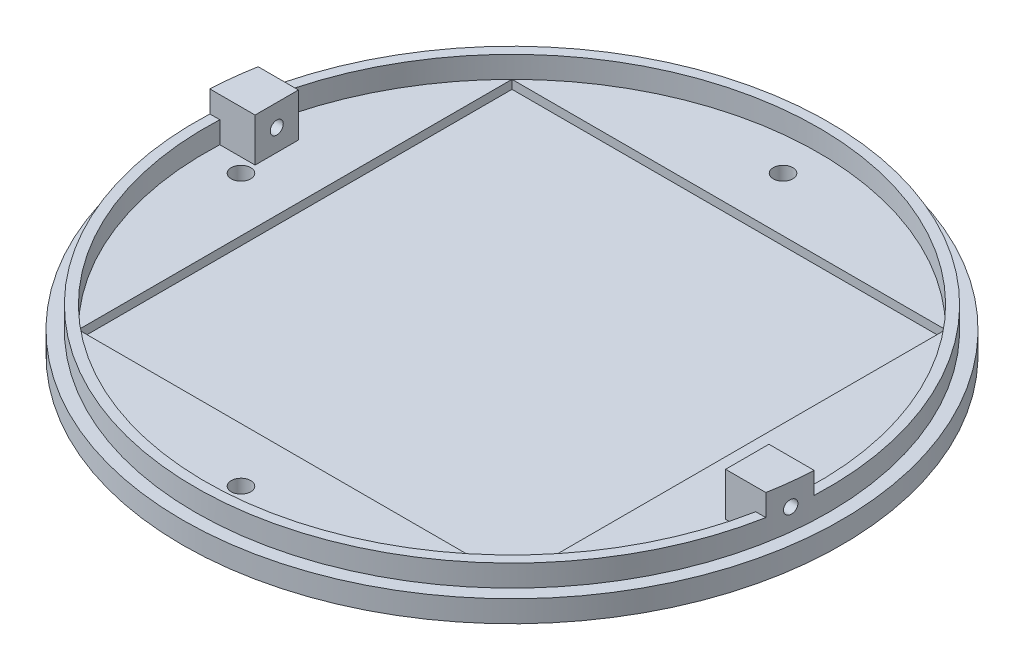
SolidWorks part; units mm, degrees
material "Custom Plastic"
ref_plane "Front Plane" through (0, 0, 0) normal (0, 0, 1) x (1, 0, 0)
ref_plane "Top Plane" through (0, 0, 0) normal (0, 1, 0) x (1, 0, 0)
ref_plane "Right Plane" through (0, 0, 0) normal (1, 0, 0) x (0, 0, -1)
sketch "Sketch1" plane through (0, 0, 0) normal (0, 1, 0) x (1, 0, 0)
  line L0 (0, 0) -> (0, -17.9724) construction
  line L1 (-50, -50) -> (50, -50)
  line L2 (-50, -50) -> (-50, 50)
  line L3 (-50, 50) -> (50, 50)
  line L4 (50, -50) -> (50, 50)
  line L5 (-50, -50) -> (50, 50) construction
  line L6 (-50, 50) -> (50, -50) construction
  line L7 (0, 0) -> (14.9739, 0) construction
  line L8 (0, 62.5) -> (14.3316, 62.5) construction
  line L9 (0, 76) -> (25.822, 76) construction
  circle A0 centre (0, 0) radius 76
  circle A1 centre (0, 0) radius 62.5 construction
  circle A2 centre (0, 62.5) radius 6.25
  circle A3 centre (62.5, 0) radius 6.25
  circle A4 centre (0, -62.5) radius 6.25
  circle A5 centre (-62.5, 0) radius 6.25
  dimension "D1" = 152
  dimension "D4" = 125
  dimension "D5" = 12.5
  dimension "D2" = 100
  dimension "D3" = 100
extrude "Boss-Extrude1" add sketch "Sketch1" along normal blind 5 contours L2 L1 L4 L3 | A0
sketch "Sketch3" plane through (0, 5, 0) normal (0, 1, 0) x (1, 0, 0)
  line L1 (-50, -50) -> (50, -50)
  line L2 (-50, -50) -> (-50, 50)
  line L3 (-50, 50) -> (50, 50)
  line L4 (50, -50) -> (50, 50)
  line L5 (-50, -50) -> (50, 50) construction
  line L6 (-50, 50) -> (50, -50) construction
  point P0 (0, 0)
extrude "Boss-Extrude2" add sketch "Sketch3" against normal blind 5
extrude "Cut-Extrude1" cut sketch "Sketch3<2>" against normal blind 2
sketch "Sketch3<2>" plane through (0, 5, 0) normal (0, 1, 0) x (1, 0, 0) same geometry as "Sketch3"
sketch "Sketch6" plane through (0, 5, 0) normal (0, 1, 0) x (1, 0, 0)
  circle A0 centre (0, 0) radius 62.5 construction
  circle A1 centre (0, 62.5) radius 2.25
  circle A2 centre (62.5, 0) radius 2.25
  circle A3 centre (0, -62.5) radius 2.25
  circle A4 centre (-62.5, 0) radius 2.25
  dimension "D1" = 125
  dimension "D2" = 4.5
extrude "Cut-Extrude2" cut sketch "Sketch6" against normal blind 10
sketch "Sketch8" plane through (0, 5, 0) normal (0, 1, 0) x (1, 0, 0)
  circle A2 centre (0, 0) radius 70.7107
  circle A3 centre (0, 0) radius 73
extrude "Boss-Extrude3" add sketch "Sketch8" along normal blind 5
sketch "Sketch11" plane through (0, 5, 0) normal (0, 1, 0) x (1, 0, 0)
  line L0 (62.5, -2.25) -> (62.5, -3.25)
  line L1 (62.5, -3.25) -> (72.9276, -3.25)
  line L2 (62.5, 2.25) -> (62.5, -2.25)
  line L3 (62.5, -3.25) -> (62.5, -13.25)
  line L4 (62.5, -13.25) -> (71.7874, -13.25)
  line L5 (62.5, -13.25) -> (62.5, -3.25)
  line L6 (0, 0) -> (0, 38.8492) construction
  line L7 (1000, 0) -> (0, 0) construction
  circle A0 centre (62.5, 0) radius 2.25 construction
  circle A3 centre (0, 0) radius 73 construction
  circle A4 centre (0, 0) radius 73
  point P23 (0, 0)
  arc M6 (50, -50) -> (50, 50) centre (0, 0) ccw
  dimension "D1" = 1
  dimension "D2" = 10
extrude "Boss-Extrude4" add sketch "Sketch11" along normal blind 10 contours L3 L4 L1 M6 region at (66.3415, 5, 8.1221)
sketch "Sketch12" plane through (0, 10, 0) normal (0, 1, 0) x (1, 0, 0)
  line L0 (70.636, -3.25) -> (72.9276, -3.25)
  line L1 (69.4582, -13.25) -> (71.7874, -13.25)
  circle A0 centre (0, 0) radius 73 construction
  arc A1 (69.4582, -13.25) -> (70.636, -3.25) centre (0, 0) ccw construction
  circle A2 centre (0, 0) radius 73
  arc A3 (69.4582, -13.25) -> (70.636, -3.25) centre (0, 0) ccw
  circle M3 centre (0, 0) radius 73
  arc M4 (70.636, -3.25) -> (69.4582, -13.25) centre (0, 0) cw
extrude "Boss-Extrude5" add sketch "Sketch12" along normal blind 5 contours L1 L0 M4 M3 region at (71.3192, 10, 8.2635)
sketch "Sketch13" plane through (0, 5, 0) normal (0, 1, 0) x (1, 0, 0)
  line L0 (-62.5, 0) -> (-62.5, 2.25)
  line L1 (-62.5, 2.25) -> (-62.5, 3.25)
  line L2 (-62.5, 3.25) -> (-62.5, 13.25)
  line L3 (-62.5, 13.25) -> (-71.7874, 13.25)
  line L4 (-62.5, 3.25) -> (-72.9276, 3.25)
  circle A0 centre (-62.5, 0) radius 2.25 construction
  circle A1 centre (0, 0) radius 73 construction
  circle A2 centre (0, 0) radius 73
  arc M6 (-50, 50) -> (-50, -50) centre (0, 0) ccw
  dimension "D1" = 1
  dimension "D2" = 10
extrude "Boss-Extrude7" add sketch "Sketch13" along normal blind 10 contours L4 L2 L3 M6 region at (-66.3415, 5, -8.1221)
sketch "Sketch14" plane through (0, 10, 0) normal (0, 1, 0) x (1, 0, 0)
  line L0 (-69.4582, 13.25) -> (-71.7874, 13.25)
  line L1 (-70.636, 3.25) -> (-72.9276, 3.25)
  arc A0 (72.9276, -3.25) -> (71.7874, -13.25) centre (0, 0) ccw construction
  arc A1 (-71.7874, 13.25) -> (-72.9276, 3.25) centre (0, 0) ccw
  arc A2 (-69.4582, 13.25) -> (-70.636, 3.25) centre (0, 0) ccw construction
  arc A3 (-69.4582, 13.25) -> (-70.636, 3.25) centre (0, 0) ccw
extrude "Boss-Extrude8" add sketch "Sketch14" along normal blind 5 contours L0 A1 L1 A3
sketch "Sketch17" plane through (-62.5, 0, 0) normal (1, 0, 0) x (0, 0, -1)
  line L0 (8.25, 5) -> (8.25, 15)
  line L1 (3.25, 5) -> (13.25, 5) construction
  line L2 (3.25, 15) -> (13.25, 15) construction
  circle A0 centre (8.25, 10) radius 1.5
  dimension "D1" = 3
extrude "Cut-Extrude3" cut sketch "Sketch17" against normal blind 27 contours L0 A0 | L0 A0 region at (-62.5, 10, -7.6134) region at (-62.5, 10, -8.8866)
sketch "Sketch18" plane through (62.5, 0, 0) normal (-1, 0, 0) x (0, 0, 1)
  line L0 (8.25, 15) -> (8.25, 5)
  line L1 (3.25, 15) -> (13.25, 15) construction
  line L2 (3.25, 5) -> (13.25, 5) construction
  circle A0 centre (8.25, 10) radius 1.5
  dimension "D1" = 3
extrude "Cut-Extrude4" cut sketch "Sketch18" against normal blind 27 contours L0 A0 | L0 A0 region at (62.5, 10, 8.8866) region at (62.5, 10, 7.6134)
